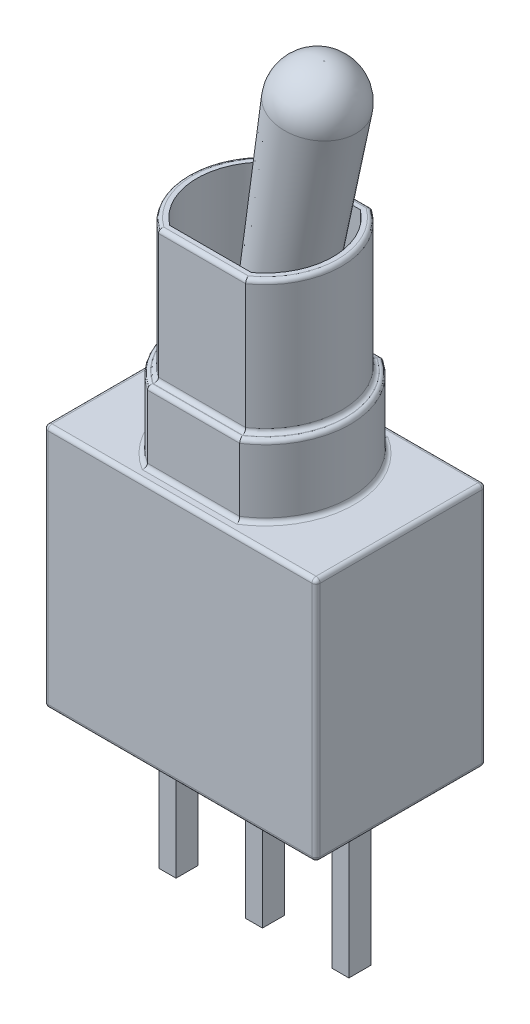
SolidWorks part; units mm, degrees
ref_plane "Front Plane" through (0, 0, 0) normal (0, 0, 1) x (1, 0, 0)
ref_plane "Top Plane" through (0, 0, 0) normal (0, 1, 0) x (1, 0, 0)
ref_plane "Right Plane" through (0, 0, 0) normal (1, 0, 0) x (0, 0, -1)
sketch "Sketch1" plane through (0, 0, 0) normal (0, 1, 0) x (1, 0, 0)
  line L1 (-4, 2.5) -> (4, 2.5)
  line L2 (-4, 2.5) -> (-4, -2.5)
  line L3 (-4, -2.5) -> (4, -2.5)
  line L4 (4, 2.5) -> (4, -2.5)
  line L5 (-4, 2.5) -> (4, -2.5) construction
  line L6 (-4, -2.5) -> (4, 2.5) construction
  point P0 (0, 0)
  dimension "D1" = 5
  dimension "D2" = 8
extrude "Boss-Extrude1" add sketch "Sketch1" along normal blind 7.2
sketch "Sketch2" plane through (0, 7.2, 0) normal (0, 1, 0) x (1, 0, 0)
  line L1 (1.3565, -2.1) -> (-1.3565, -2.1)
  line L2 (1.3565, -2.1) -> (1.3565, 2.1)
  line L3 (1.3565, 2.1) -> (-1.3565, 2.1)
  line L4 (-1.3565, -2.1) -> (-1.3565, 2.1)
  line L5 (1.3565, -2.1) -> (-1.3565, 2.1) construction
  line L6 (1.3565, 2.1) -> (-1.3565, -2.1) construction
  circle A0 centre (0, 0) radius 2.5
  dimension "D1" = 5
  dimension "D2" = 4.2
extrude "Boss-Extrude2" add sketch "Sketch2" along normal blind 2.1 contours L4 A0 | L4 L1 L2 L3 | L2 A0 region at (0, 7.2, 0) region at (1.8242, 7.2, 0) region at (-1.8242, 7.2, 0)
sketch "Sketch3" plane through (0, 9.3, 0) normal (0, 1, 0) x (1, 0, 0)
  line L4 (-1.2806, -1.85) -> (1.2806, -1.85)
  line L5 (1.2806, 1.85) -> (-1.2806, 1.85)
  line L6 (-1.2806, -1.85) -> (1.2806, -1.85)
  line L7 (1.2806, 1.85) -> (-1.2806, 1.85)
  arc A4 (-1.2806, 1.85) -> (-1.2806, -1.85) centre (0, 0) ccw
  arc A5 (1.2806, -1.85) -> (1.2806, 1.85) centre (0, 0) ccw
  arc A6 (-1.2806, 1.85) -> (-1.2806, -1.85) centre (0, 0) ccw
  arc A7 (1.2806, -1.85) -> (1.2806, 1.85) centre (0, 0) ccw
  dimension "D1" = 0.25
extrude "Boss-Extrude3" add sketch "Sketch3" along normal offset from surface (3.9 mm away) 6 up to face at (0, 7.2, 0) offset beyond the face yes
sketch "Sketch4" plane through (0, 13.2, 0) normal (0, 1, 0) x (1, 0, 0)
  line L4 (1.2, 1.6) -> (-1.2, 1.6)
  line L5 (-1.2, -1.6) -> (1.2, -1.6)
  line L6 (1.2, 1.6) -> (-1.2, 1.6)
  line L7 (-1.2, -1.6) -> (1.2, -1.6)
  arc A4 (-1.2, 1.6) -> (-1.2, -1.6) centre (0, 0) ccw
  arc A5 (1.2, -1.6) -> (1.2, 1.6) centre (0, 0) ccw
  arc A6 (-1.2, 1.6) -> (-1.2, -1.6) centre (0, 0) ccw
  arc A7 (1.2, -1.6) -> (1.2, 1.6) centre (0, 0) ccw
  dimension "D1" = 0.25
extrude "Cut-Extrude1" cut sketch "Sketch4" against normal blind 6
ref_plane "Plane1" through (0, 8.2, 0) normal (0, 1, 0) x (1, 0, 0)
ref_axis "Axis1" through (0, 8.2, -2.75) along (0, 0, 1)
ref_plane "Plane2" through (-1.4023, 0.2473, 0) normal (-0.9848, 0.1736, 0) x (0, 0, 1)
ref_plane "Plane3" through (1.4023, 7.9527, 0) normal (-0.1736, -0.9848, 0) x (0, 0, 1)
sketch "Sketch5" plane through (1.4023, 7.9527, 0) normal (-0.1736, -0.9848, 0) x (0, 0, 1)
  line L0 (3.025, 1.4239) -> (-3.025, 1.4239) construction
  line L1 (0, 4.8006) -> (0, -5.28) construction
  circle A0 centre (0, 1.4239) radius 0.9
  dimension "D1" = 1.8
ref_plane "Plane4" through (3.1388, 17.8008, 0) normal (-0.1736, -0.9848, 0) x (0, 0, 1)
sketch "Sketch6" plane through (3.1388, 17.8008, 0) normal (-0.1736, -0.9848, 0) x (0, 0, 1)
  circle A0 centre (0, 1.4239) radius 1.2
  dimension "D1" = 2.4
loft "Loft1" add profiles "Sketch6", "Sketch5" connector at (1.4738, 18.0944, 1.17) connector at (-0.0526, 8.2093, 0.8984)
fillet "Fillet1" radius 1.15 1 edges at (2.9183, 17.8397, 0)
sketch "Sketch7" plane through (0, 0, 0) normal (0, -1, 0) x (1, 0, 0)
  line L0 (-4, 0) -> (4, 0) construction
  line L1 (-4, -2.5) -> (-4, 2.5) construction
  line L2 (4, 2.5) -> (4, -2.5) construction
  line L3 (0, 2.5) -> (0, -2.5) construction
  line L4 (-4, 2.5) -> (4, 2.5) construction
  line L5 (4, -2.5) -> (-4, -2.5) construction
  line L6 (2.79, 0.325) -> (2.79, -0.325)
  line L7 (-0.25, 0.325) -> (0.25, 0.325)
  line L8 (-0.25, 0.325) -> (-0.25, -0.325)
  line L9 (-0.25, -0.325) -> (0.25, -0.325)
  line L10 (0.25, 0.325) -> (0.25, -0.325)
  line L11 (-0.25, 0.325) -> (0.25, -0.325) construction
  line L12 (-0.25, -0.325) -> (0.25, 0.325) construction
  line L13 (-2.79, 0.325) -> (-2.29, 0.325)
  line L14 (-2.79, 0.325) -> (-2.79, -0.325)
  line L15 (-2.79, -0.325) -> (-2.29, -0.325)
  line L16 (-2.29, 0.325) -> (-2.29, -0.325)
  line L17 (-2.79, 0.325) -> (-2.29, -0.325) construction
  line L18 (-2.79, -0.325) -> (-2.29, 0.325) construction
  line L19 (2.79, 0.325) -> (2.29, 0.325)
  line L20 (2.29, 0.325) -> (2.29, -0.325)
  line L21 (2.79, -0.325) -> (2.29, -0.325)
  point P12 (0, 0)
  point P18 (-2.54, 0)
  dimension "D1" = 0.65
  dimension "D2" = 0.5
  dimension "D3" = 2.54
extrude "Boss-Extrude4" add sketch "Sketch7" along normal blind 4.6
fillet "Fillet2" radius 0.12 28 edges at (0, 9.3, -2.1) (2.5, 9.3, 0) (0, 9.3, 2.1) (-2.5, 9.3, 0) (0, 9.3, 1.85) (2.25, 9.3, 0) (0, 9.3, -1.85) (-2.25, 9.3, 0) (-4, 0, 0) (-4, 3.6, -2.5) (0, 0, -2.5) (4, 3.6, -2.5) (4, 0, 0) (-4, 3.6, 2.5) (4, 3.6, 2.5) (0, 0, 2.5) (0, 7.2, 2.5) (-4, 7.2, 0) (0, 7.2, -2.5) (4, 7.2, 0) (0, 7.2, 2.1) (2.5, 7.2, 0) (0, 7.2, -2.1) (-2.5, 7.2, 0) (0, 13.2, 1.85) (-2.25, 13.2, 0) (0, 13.2, -1.85) (2.25, 13.2, 0)
